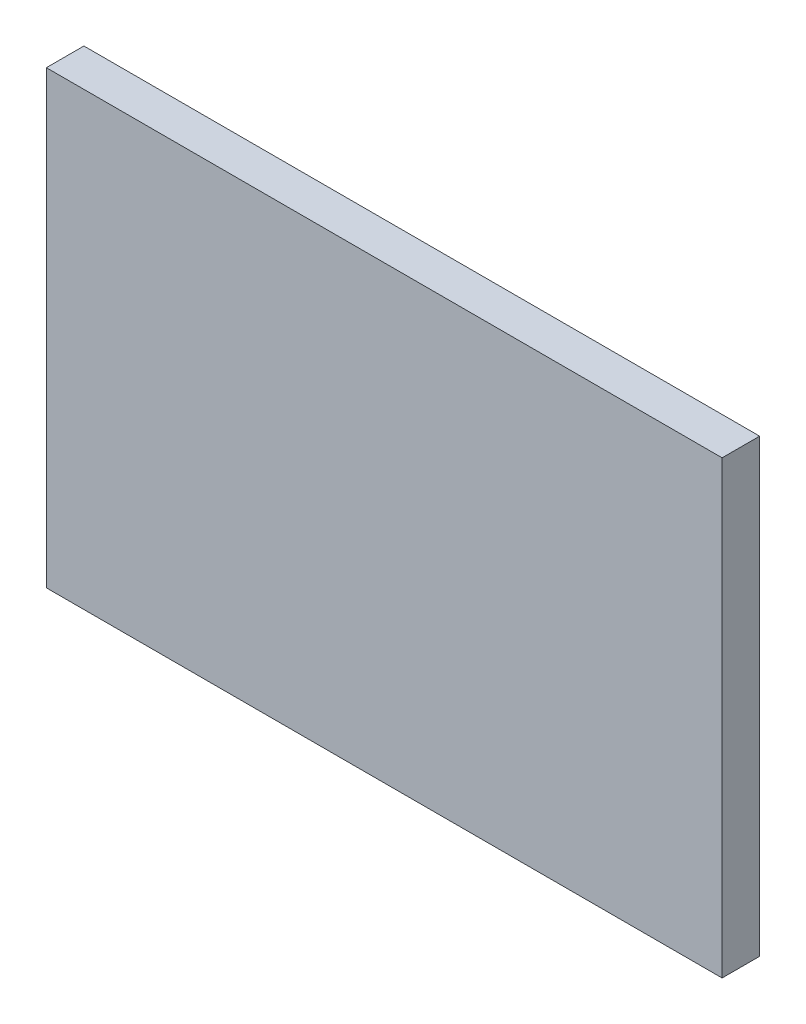
SolidWorks part; units mm, degrees
material "1060-H12"
ref_plane "Alzado" through (0, 0, 0) normal (0, 0, 1) x (1, 0, 0)
ref_plane "Planta" through (0, 0, 0) normal (0, 1, 0) x (1, 0, 0)
ref_plane "Vista lateral" through (0, 0, 0) normal (1, 0, 0) x (0, 0, -1)
sketch "Croquis1" plane through (0, 0, 0) normal (0, 0, 1) x (1, 0, 0)
  line L1 (-45, -30) -> (45, -30)
  line L2 (-45, -30) -> (-45, 30)
  line L3 (-45, 30) -> (45, 30)
  line L4 (45, -30) -> (45, 30)
  line L5 (-45, -30) -> (45, 30) construction
  line L6 (-45, 30) -> (45, -30) construction
  point P0 (0, 0)
  dimension "D1" = 60
  dimension "D2" = 90
extrude "Saliente-Extruir1" add sketch "Croquis1" along normal blind 5
